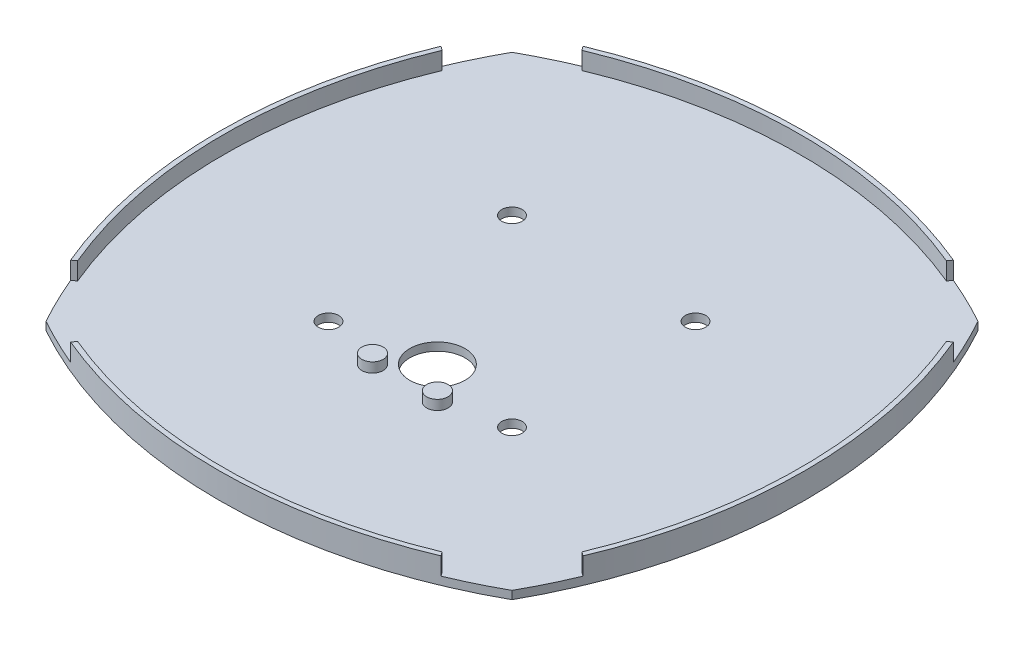
SolidWorks part; units mm, degrees
ref_plane "Front Plane" through (0, 0, 0) normal (0, 0, 1) x (1, 0, 0)
ref_plane "Top Plane" through (0, 0, 0) normal (0, 1, 0) x (1, 0, 0)
ref_plane "Right Plane" through (0, 0, 0) normal (1, 0, 0) x (0, 0, -1)
sketch "Sketch1" plane through (0, 0, 0) normal (0, 1, 0) x (1, 0, 0)
  line L0 (175.429, 389.4302) -> (225.429, 389.4742) construction
  dimension "D1" = 50
sketch "Sketch3" plane through (0, 0, 0) normal (0, 1, 0) x (1, 0, 0)
  line L2 (199.3319, -52.9004) -> (358.0133, -52.9004) construction
  line L3 (199.3319, -52.9004) -> (199.3319, 49.5555) construction
  arc A5 (130.4554, 15.9761) -> (130.4554, -121.7769) centre (256.8431, -52.9004) ccw construction
  arc A6 (268.2084, 15.9761) -> (130.4554, 15.9761) centre (199.3319, -110.4116) ccw construction
  arc A7 (268.2084, -121.7769) -> (268.2084, 15.9761) centre (141.8208, -52.9004) ccw construction
  arc A9 (130.4554, -121.7769) -> (268.2084, -121.7769) centre (199.3319, 4.6107) ccw construction
  arc A12 (271.1535, 18.9212) -> (127.5103, 18.9212) centre (199.3319, -110.4116) ccw
  arc A14 (127.5103, 18.9212) -> (127.5103, -124.722) centre (256.8431, -52.9004) ccw
  arc A15 (127.5103, -124.722) -> (271.1535, -124.722) centre (199.3319, 4.6107) ccw
  arc A16 (271.1535, -124.722) -> (271.1535, 18.9212) centre (141.8208, -52.9004) ccw
  point P0 (199.3319, -52.9004)
  point P15 (199.3319, -52.9004)
  dimension "D1" = 4
extrude "Boss-Extrude1" add sketch "Sketch3" along normal blind 2.5
sketch "Sketch5" plane through (0, 2.5, 0) normal (0, 1, 0) x (1, 0, 0)
  line L0 (141.8208, -52.9004) -> (256.8431, -52.9004) construction
  line L1 (199.3319, 4.6107) -> (199.3319, -110.4116) construction
  line L2 (121.6116, -109.0803) -> (120.3642, -109.9865)
  line L3 (143.1521, -130.6208) -> (142.2458, -131.8681)
  line L4 (277.0523, 3.2794) -> (278.2996, 4.1857)
  line L5 (255.5118, 24.8199) -> (256.418, 26.0673)
  line L6 (277.0523, -109.0803) -> (278.2996, -109.9865)
  line L7 (255.5118, -130.6208) -> (256.418, -131.8681)
  line L8 (121.6125, 3.2817) -> (120.3652, 4.1879)
  line L9 (143.1498, 24.819) -> (142.2436, 26.0663)
  line L10 (110.4063, 20.1528) -> (110.4063, -83.3423) construction
  line L11 (288.2576, 27.2093) -> (288.2576, -79.0531) construction
  line L12 (35.0838, 36.0252) -> (347.5932, 36.0252) construction
  line L13 (32.3242, -141.8261) -> (353.5329, -141.8261) construction
  arc A8 (128.614, -123.6184) -> (270.0499, -123.6184) centre (199.3319, 4.6107) ccw
  arc A9 (270.0499, -123.6184) -> (270.0499, 17.8175) centre (141.8208, -52.9004) ccw
  arc A10 (270.0499, 17.8175) -> (128.614, 17.8175) centre (199.3319, -110.4116) ccw
  arc A11 (128.614, 17.8175) -> (128.614, -123.6184) centre (256.8431, -52.9004) ccw
  arc A12 (143.1521, -130.6208) -> (255.5118, -130.6208) centre (199.3319, 4.6107) ccw
  arc A13 (277.0523, -109.0803) -> (277.0523, 3.2794) centre (141.8208, -52.9004) ccw
  arc A14 (255.5118, 24.8199) -> (143.1498, 24.819) centre (199.3319, -110.4116) ccw
  arc A15 (121.6125, 3.2817) -> (121.6116, -109.0803) centre (256.8431, -52.9004) ccw
  arc A21 (271.1535, 18.9212) -> (127.5103, 18.9212) centre (199.3319, -110.4116) ccw
  arc A22 (271.1535, -124.722) -> (271.1535, 18.9212) centre (141.8208, -52.9004) ccw
  arc A23 (127.5103, -124.722) -> (271.1535, -124.722) centre (199.3319, 4.6107) ccw
  arc A24 (127.5103, 18.9212) -> (127.5103, -124.722) centre (256.8431, -52.9004) ccw
  arc A25 (256.418, 26.0673) -> (142.2436, 26.0663) centre (199.3319, -110.4116) ccw
  arc A26 (278.2996, -109.9865) -> (278.2996, 4.1857) centre (141.8208, -52.9004) ccw
  arc A27 (142.2458, -131.8681) -> (256.418, -131.8681) centre (199.3319, 4.6107) ccw
  arc A28 (120.3652, 4.1879) -> (120.3642, -109.9865) centre (256.8431, -52.9004) ccw
  dimension "D2" = 36
  dimension "D3" = 36
  dimension "D4" = 36
  dimension "D5" = 36
  dimension "D6" = 36
  dimension "D7" = 36
  dimension "D8" = 36
  dimension "D9" = 36
  dimension "D1" = 1.5
  dimension "D10" = 0
extrude "Boss-Extrude2" add sketch "Sketch5" along normal blind 5.4
sketch "Sketch6" plane through (0, 2.5, 0) normal (0, 1, 0) x (1, 0, 0)
  line L0 (127.5103, -124.722) -> (271.1535, 18.9212) construction
  line L1 (127.5103, 18.9212) -> (271.1535, -124.722) construction
  line L2 (199.3319, -54.185) -> (199.3319, 43.8674) construction
  circle A1 centre (199.3319, -84.7202) radius 22.5
  point P12 (199.3319, -52.9004)
  dimension "D1" = 45
ref_plane "Plane1" through (0, 60, 0) normal (0, 1, 0) x (1, 0, 0)
sketch "Sketch11" plane through (0, 2.5, 0) normal (0, 1, 0) x (1, 0, 0)
  line L0 (127.5103, -124.722) -> (271.1535, 18.9212) construction
  line L1 (127.5103, 18.9212) -> (271.1535, -124.722) construction
  line L2 (199.3319, -50.7415) -> (199.3319, 48.5237) construction
  line L3 (199.3319, -52.9004) -> (293.7423, -52.9004) construction
  circle A0 centre (171.0477, -24.6162) radius 3.15
  circle A1 centre (227.6162, -24.6162) radius 3.15
  circle A2 centre (227.6162, -81.1847) radius 3.15
  circle A3 centre (171.0477, -81.1847) radius 3.15
  circle A4 centre (199.3319, -75.9004) radius 8.5
  point P11 (199.3319, -52.9004)
  point P24 (199.3319, -52.9004)
  dimension "D2" = 6.3
  dimension "D4" = 17
  dimension "D3" = 40
  dimension "D5" = 23
  dimension "D1" = 4
extrude "Cut-Extrude2" cut sketch "Sketch11" against normal through all both and the other way through all
sketch "Sketch13" plane through (0, 2.5, 0) normal (0, 1, 0) x (1, 0, 0)
  line L0 (199.3319, -74.6137) -> (199.3319, -39.6509) construction
  line L1 (199.3319, -75.9004) -> (212.0826, -75.9004) construction
  circle A5 centre (189.3319, -85.9004) radius 3.2895
  circle A6 centre (209.3319, -85.9004) radius 3.2895
  point P1 (199.3319, -75.9004)
  point P14 (199.3319, -75.9004)
  dimension "D1" = 10
  dimension "D2" = 10
extrude "Boss-Extrude3" add sketch "Sketch13" along normal blind 3
sketch "Sketch7" plane through (0, 60, 0) normal (0, 1, 0) x (1, 0, 0)
  line L0 (199.3319, -200054.185) -> (199.3319, 200043.8674) construction
  circle A0 centre (199.3319, -97.9702) radius 9
  dimension "D1" = 18
loft "Loft1" [suppressed] add profiles "Sketch7", "Sketch6"
sketch "Sketch8" [suppressed] plane through (0, 2.5, 0) normal (0, 1, 0) x (1, 0, 0)
  line L0 (199.3319, -97.9702) -> (199.3319, -52.584) construction
  line L1 (127.5103, -124.722) -> (271.1535, 18.9212) construction
  line L2 (127.5103, 18.9212) -> (271.1535, -124.722) construction
  circle A4 centre (199.3319, -97.9702) radius 9 construction
  circle A5 centre (199.3319, -75.9004) radius 8.5
  point P0 (199.3319, -97.9702)
  point P10 (199.3319, -52.9004)
  dimension "D1" = 17
  dimension "D2" = 23
sketch "Sketch9" [suppressed] plane through (0, 60, 0) normal (0, 1, 0) x (1, 0, 0)
  circle A0 centre (199.3319, -97.9702) radius 6
  dimension "D1" = 12
loft "Cut-Loft1" [suppressed] cut profiles "Sketch9", "Sketch8"
